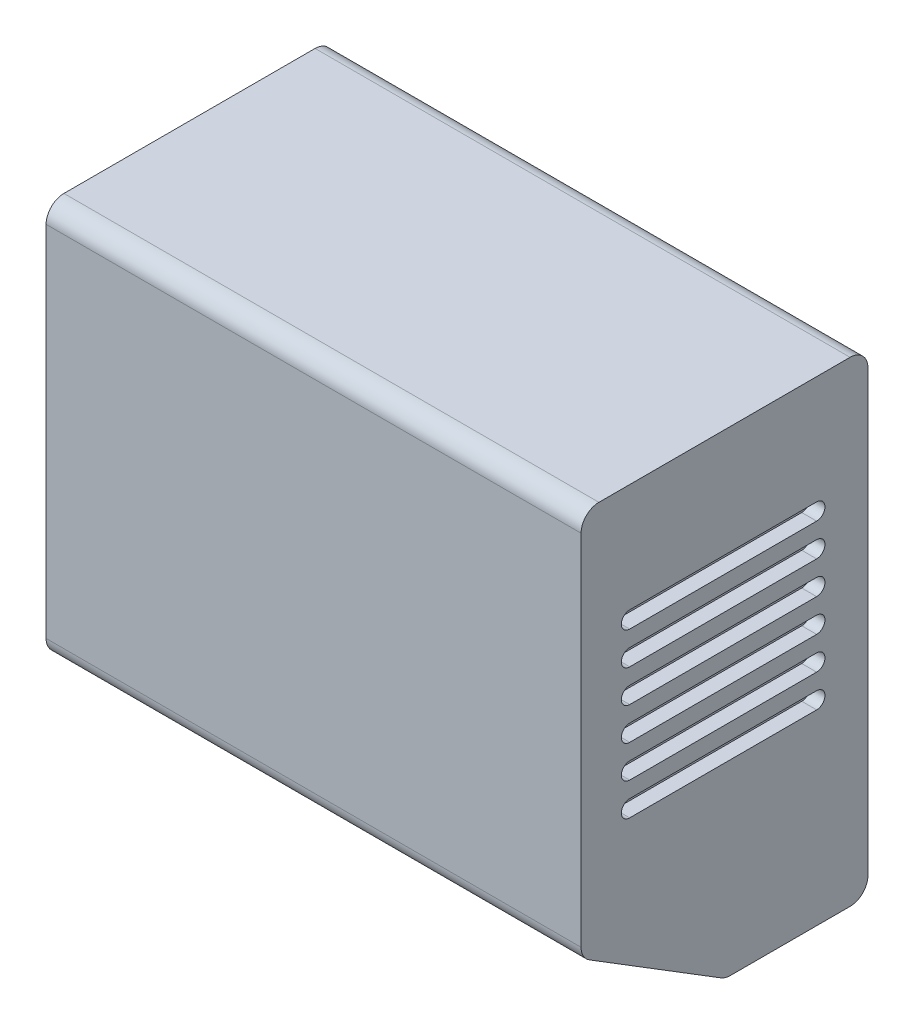
SolidWorks part; units mm, degrees
ref_plane "Plan de face" through (0, 0, 0) normal (0, 0, 1) x (1, 0, 0)
ref_plane "Plan de dessus" through (0, 0, 0) normal (0, 1, 0) x (1, 0, 0)
ref_plane "Plan de droite" through (0, 0, 0) normal (1, 0, 0) x (0, 0, -1)
sketch "Esquisse1" plane through (0, 0, 0) normal (1, 0, 0) x (0, 0, -1)
  line L0 (-48.25, 40) -> (0, 40)
  line L1 (0, 40) -> (0, 0)
  line L2 (0, 0) -> (0, -40)
  line L3 (0, -40) -> (-24, -40)
  line L4 (-24, -40) -> (-48.25, -25)
  line L5 (-48.25, -25) -> (-48.25, 40)
  dimension "D1" = 80
  dimension "D2" = 48.25
  dimension "D3" = 24
  dimension "D4" = 65
extrude "Boss.-Extru.1" add sketch "Esquisse1" along normal blind 45 and the other way blind 45
fillet "Congé1" radius 3 5 edges at (0, -40, 24) (0, -25, 48.25) (0, -40, 0) (0, 40, 0) (0, 40, 48.25)
sketch "Esquisse2" plane through (45, 0, 0) normal (1, 0, 0) x (0, 0, -1)
  line L0 (-40.0741, 20.3468) -> (-8.626, 20.3468) construction
  line L1 (-40.0741, 21.7468) -> (-8.626, 21.7468)
  line L2 (-40.0741, 18.9468) -> (-8.626, 18.9468)
  arc A0 (-40.0741, 21.7468) -> (-40.0741, 18.9468) centre (-40.0741, 20.3468) ccw
  arc A1 (-8.626, 18.9468) -> (-8.626, 21.7468) centre (-8.626, 20.3468) ccw
  point P2 (-24.3501, 20.3468)
  dimension "D1" = 2.8
extrude "Enlèv. mat.-Extru.1" cut sketch "Esquisse2" against normal blind 2.5
pattern_linear "Répétition linéaire1" count 6 spacing 5.5 along (0, -1, 0) of "Enlèv. mat.-Extru.1"
mirror "Symétrie1" about plane through (0, 0, 0) normal (1, 0, 0) of "Répétition linéaire1"
